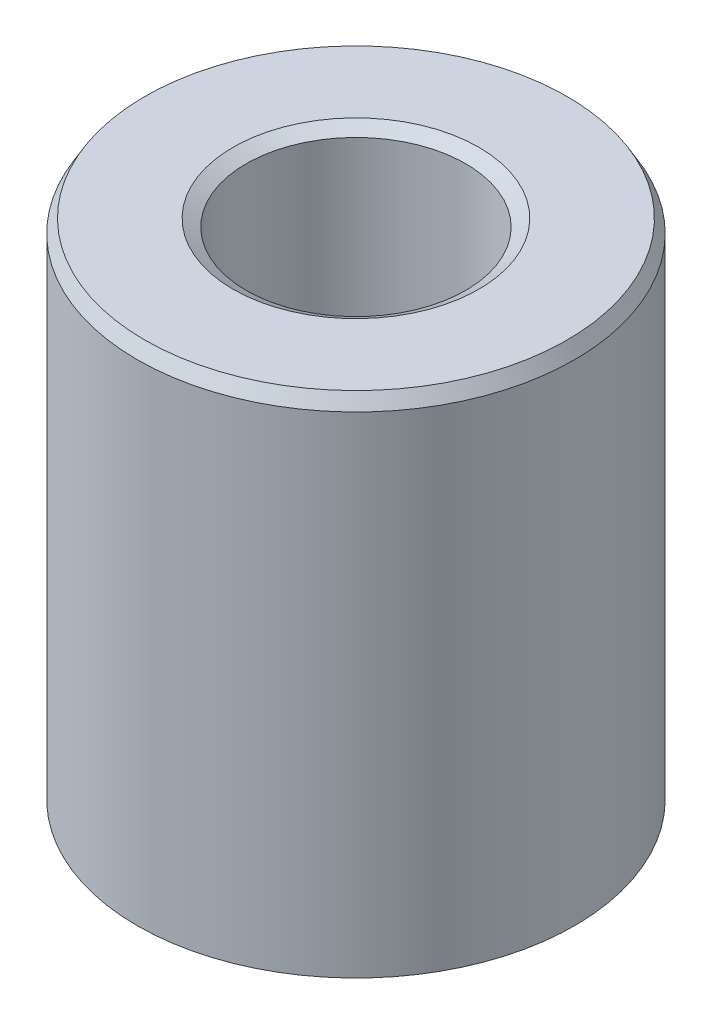
SolidWorks part; units mm, degrees
ref_plane "Front Plane" through (0, 0, 0) normal (0, 0, 1) x (1, 0, 0)
ref_plane "Top Plane" through (0, 0, 0) normal (0, 1, 0) x (1, 0, 0)
ref_plane "Right Plane" through (0, 0, 0) normal (1, 0, 0) x (0, 0, -1)
sketch "Sketch1" plane through (0, 0, 0) normal (0, 1, 0) x (1, 0, 0)
  circle A0 centre (0, 0) radius 45
  dimension "SLEEVE_OD" = 90
extrude "Boss-Extrude1" add sketch "Sketch1" along normal blind 105.1586
sketch "Sketch2" plane through (0, 0, 0) normal (0, 1, 0) x (1, 0, 0)
  circle A0 centre (0, 0) radius 22.5885
  dimension "BORE_D" = 45.1771
extrude "Cut-Extrude1" cut sketch "Sketch2" along normal through all
chamfer "Chamfer1" distance 2.713 angle 30 4 edges at (0, 105.1586, 22.5885) (0, 0, 22.5885) (0, 0, 45) (0, 105.1586, 45) first distance on face at (0, 105.1586, 22.5885) first distance on face at (0, 0, 22.5885) first distance on face at (0, 105.1586, 45)
